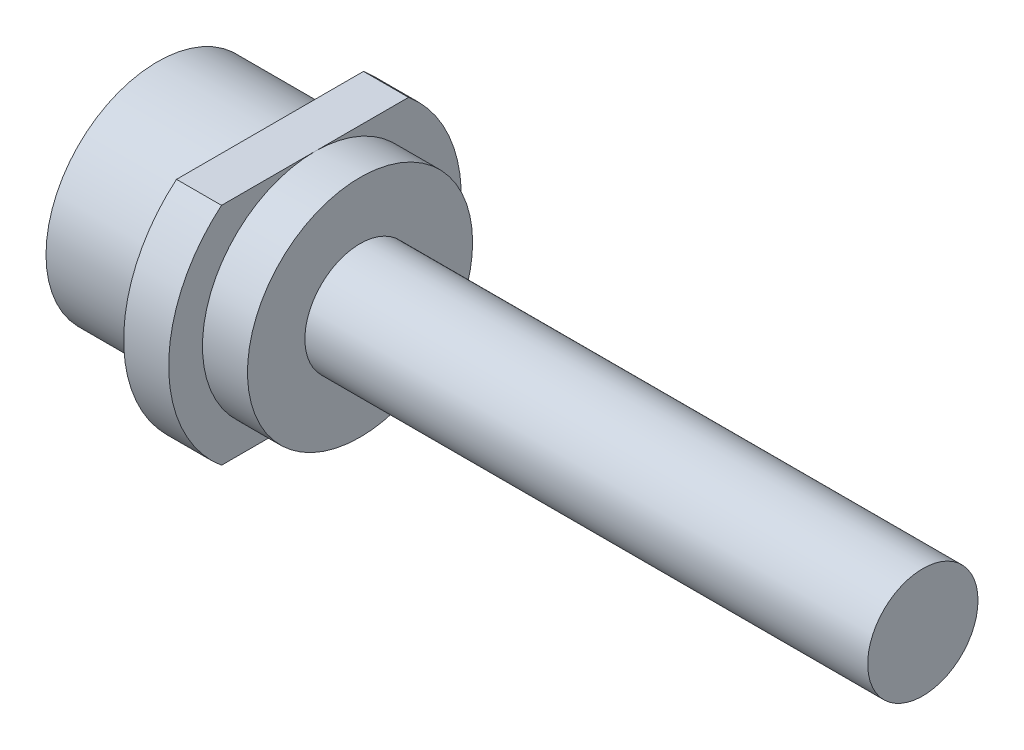
SolidWorks part; units mm, degrees
ref_plane "前视基准面" through (0, 0, 0) normal (0, 0, 1) x (1, 0, 0)
ref_plane "上视基准面" through (0, 0, 0) normal (0, 1, 0) x (1, 0, 0)
ref_plane "右视基准面" through (0, 0, 0) normal (1, 0, 0) x (0, 0, -1)
sketch "草图2" plane through (0, 0, 0) normal (1, 0, 0) x (0, 0, -1)
  line L0 (4.1533, 5) -> (-4.1533, 5)
  line L1 (4.1533, -5) -> (-4.1533, -5)
  arc A0 (-4.1533, 5) -> (-4.1533, -5) centre (0, 0) ccw
  arc A1 (4.1533, -5) -> (4.1533, 5) centre (0, 0) ccw
  dimension "D1" = 13
  dimension "D2" = 10
  dimension "D3" = 5
extrude "凸台-拉伸1" add sketch "草图2" along normal blind 2
sketch "草图3" plane through (2, 0, 0) normal (1, 0, 0) x (0, 0, -1)
  circle A0 centre (0, 0) radius 5
extrude "凸台-拉伸2" add sketch "草图3" along normal blind 2
sketch "草图4" plane through (4, 0, 0) normal (1, 0, 0) x (0, 0, -1)
  circle A0 centre (0, 0) radius 2.45
  dimension "D1" = 4.9
extrude "凸台-拉伸3" add sketch "草图4" along normal blind 25
sketch "草图5" plane through (0, 0, 0) normal (-1, 0, 0) x (0, 0, 1)
  circle A0 centre (0, 0) radius 4.95
extrude "凸台-拉伸4" add sketch "草图5" along normal blind 5
